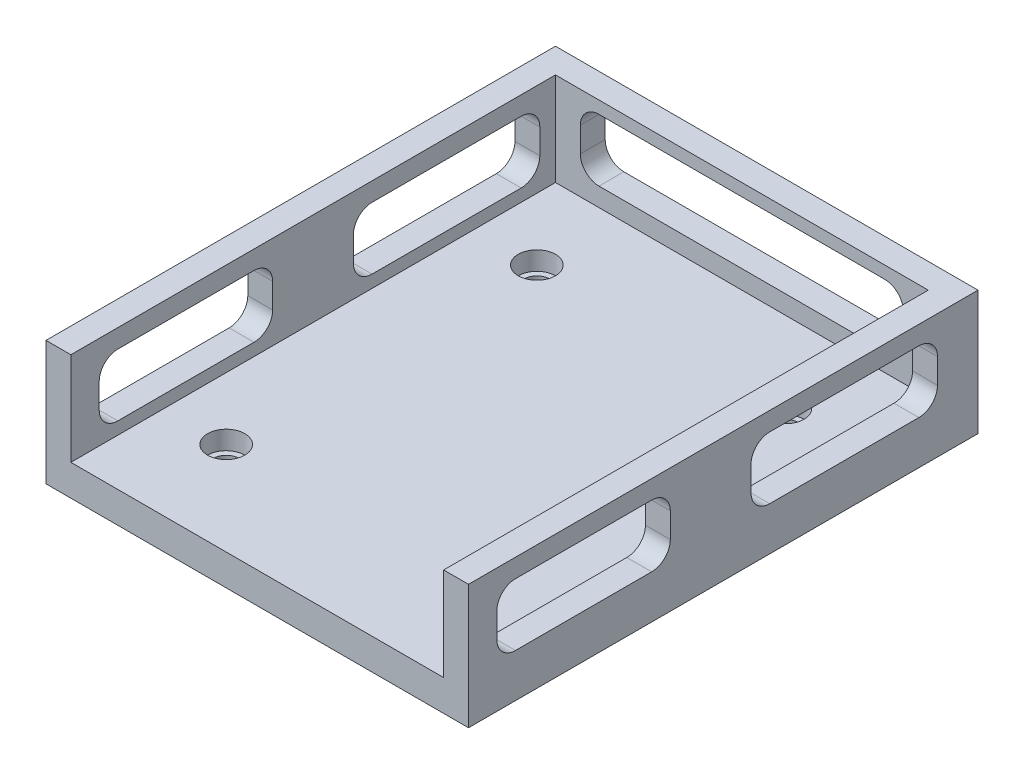
SolidWorks part; units mm, degrees
ref_plane "前视基准面" through (0, 0, 0) normal (0, 0, 1) x (1, 0, 0)
ref_plane "上视基准面" through (0, 0, 0) normal (0, 1, 0) x (1, 0, 0)
ref_plane "右视基准面" through (0, 0, 0) normal (1, 0, 0) x (0, 0, -1)
other "Configuration Table"
sketch "草图1" plane through (0, 0, 0) normal (0, 1, 0) x (1, 0, 0)
  line L0 (0, 50.5287) -> (0, -52.3733) construction
  line L1 (0, 44.2044) -> (-30, 44.2044)
  line L2 (-30, 44.2044) -> (-30, -33.7956)
  line L3 (-30, -33.7956) -> (0, -33.7956)
  line L4 (0, 44.2044) -> (30, 44.2044)
  line L5 (30, 44.2044) -> (30, -33.7956)
  line L6 (30, -33.7956) -> (0, -33.7956)
  dimension "D1" = 78
  dimension "D2" = 30
  dimension "D3" = 30
extrude "凸台-拉伸1" add sketch "草图1" along normal blind 5
sketch "草图2" plane through (0, 5, 0) normal (0, 1, 0) x (1, 0, 0)
  line L0 (-30, -33.7956) -> (-34, -33.7956)
  line L1 (-34, -33.7956) -> (-34, 48.2044)
  line L2 (-34, 48.2044) -> (34, 48.2044)
  line L3 (34, 48.2044) -> (34, -33.7956)
  line L4 (34, -33.7956) -> (30, -33.7956)
  line L5 (-30, 44.2044) -> (-30, -33.7956) construction
  line L6 (30, 44.2044) -> (-30, 44.2044) construction
  line L7 (30, -33.7956) -> (30, 44.2044) construction
  line L8 (30, -33.7956) -> (30, 44.2044)
  line L9 (30, 44.2044) -> (-30, 44.2044)
  line L10 (-30, 44.2044) -> (-30, -33.7956)
  dimension "D1" = 4
  dimension "D2" = 4
  dimension "D3" = 4
extrude "凸台-拉伸2" add sketch "草图2" against normal up to surface (5 mm away) and the other way blind 15 up to face at (0, 0, -5.2044)
sketch "草图3" plane through (0, 5, 0) normal (0, 1, 0) x (1, 0, 0)
  line L0 (0, 38.5426) -> (0, -38.0618) construction
  line L1 (30, 44.2044) -> (-30, 44.2044) construction
  circle A0 centre (-20, 31.2044) radius 3
  circle A1 centre (20, 31.2044) radius 3
  circle A2 centre (-20, -18.7956) radius 3
  circle A3 centre (20, -18.7956) radius 3
  dimension "D1" = 6
  dimension "D2" = 6
  dimension "D3" = 20
  dimension "D4" = 13
  dimension "D5" = 20
  dimension "D6" = 13
  dimension "D7" = 50
  dimension "D8" = 6
  dimension "D9" = 6
  dimension "D10" = 20
  dimension "D11" = 20
extrude "切除-拉伸1" cut sketch "草图3" against normal blind 3
sketch "草图4" plane through (0, 2, 0) normal (0, 1, 0) x (1, 0, 0)
  circle A0 centre (-20, 31.2044) radius 2.1
  circle A1 centre (20, 31.2044) radius 2.1
  circle A2 centre (20, -18.7956) radius 2.1
  circle A3 centre (-20, -18.7956) radius 2.1
  dimension "D1" = 4.2
extrude "切除-拉伸2" cut sketch "草图4" against normal blind 10
sketch "草图5" plane through (-34, 0, 0) normal (-1, 0, 0) x (0, 0, 1)
  line L0 (-41.6802, 17) -> (-41.6802, 7)
  line L1 (-41.6802, 7) -> (-11.6802, 7)
  line L2 (-11.6802, 7) -> (-11.6802, 17)
  line L6 (-48.2044, 20) -> (33.7956, 20) construction
  line L7 (-41.6802, 17) -> (-11.6802, 17)
  line L8 (1.3198, 17) -> (1.3198, 7)
  line L9 (1.3198, 7) -> (29.2316, 7)
  line L10 (29.2316, 7) -> (29.2316, 17)
  line L11 (29.2316, 17) -> (1.3198, 17)
  dimension "D1" = 10
  dimension "D2" = 10
  dimension "D3" = 13
  dimension "D4" = 13
extrude "切除-拉伸3" cut sketch "草图5" against normal through all both and the other way through all
fillet "圆角1" radius 3 16 edges at (32, 7, -41.6802) (32, 17, -41.6802) (32, 17, -11.6802) (32, 7, -11.6802) (32, 17, 1.3198) (32, 17, 29.2316) (-32, 17, 29.2316) (-32, 17, 1.3198) (-32, 7, -11.6802) (-32, 17, -11.6802) (-32, 17, -41.6802) (-32, 7, -41.6802) (32, 7, 1.3198) (32, 7, 29.2316) (-32, 7, 29.2316) (-32, 7, 1.3198)
sketch "草图6" plane through (0, 0, -44.2044) normal (0, 0, 1) x (1, 0, 0)
  line L0 (0, 28.6634) -> (0, -10.911) construction
  line L1 (0, 18) -> (-26, 18)
  line L2 (-26, 18) -> (-26, 8)
  line L3 (-26, 8) -> (26, 8)
  line L4 (26, 8) -> (26, 18)
  line L5 (26, 18) -> (0, 18)
  line L6 (-30, 20) -> (30, 20) construction
  dimension "D1" = 26
  dimension "D2" = 10
  dimension "D3" = 2
  dimension "D4" = 26
extrude "切除-拉伸4" cut sketch "草图6" against normal through all both
fillet "圆角2" radius 3 4 edges at (26, 18, -46.2044) (26, 8, -46.2044) (-26, 8, -46.2044) (-26, 18, -46.2044)
